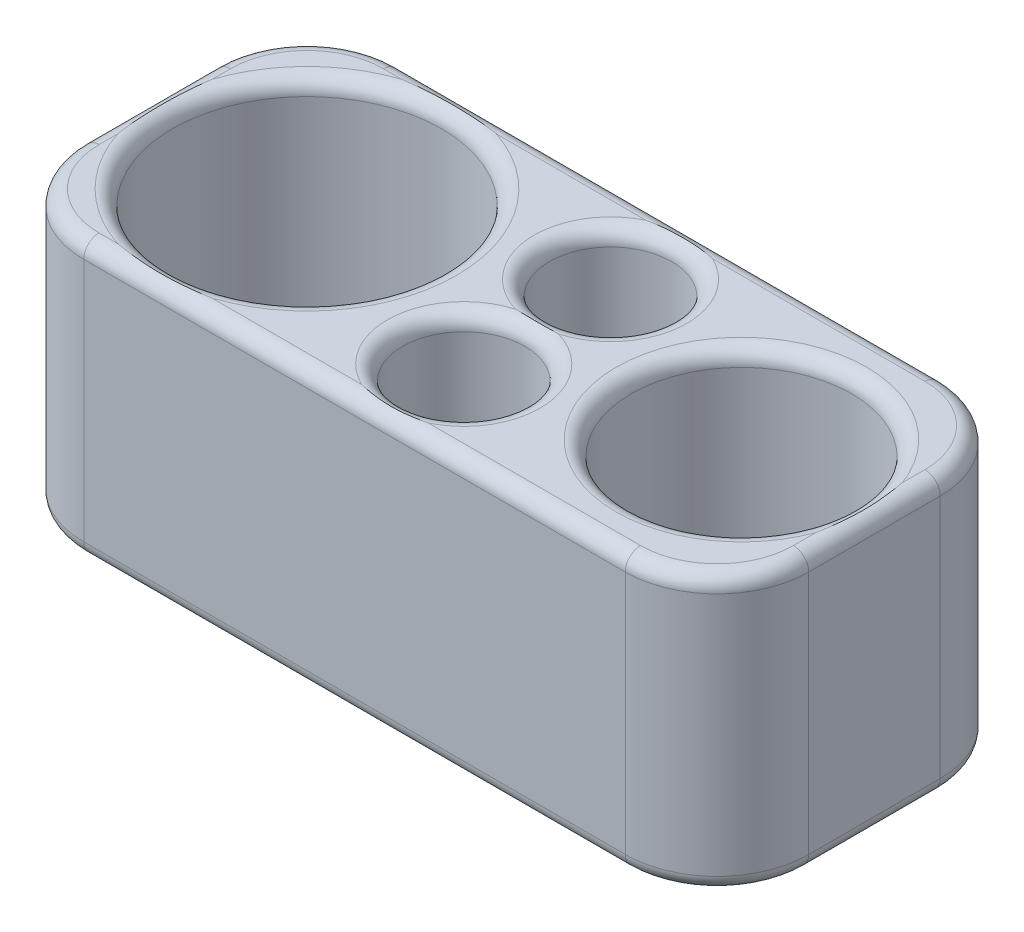
SolidWorks part; units mm, degrees
ref_plane "Front Plane" through (0, 0, 0) normal (0, 0, 1) x (1, 0, 0)
ref_plane "Top Plane" through (0, 0, 0) normal (0, 1, 0) x (1, 0, 0)
ref_plane "Right Plane" through (0, 0, 0) normal (1, 0, 0) x (0, 0, -1)
sketch "Sketch2" plane through (0, 0, 0) normal (0, 1, 0) x (1, 0, 0)
  line L0 (-7.9766, -4.2441) -> (-3.4391, -5.6909) construction
  line L1 (-35.2563, -13.97) -> (35.2563, -13.97) construction
  line L2 (-35.2563, -13.97) -> (-35.2563, 13.97) construction
  line L3 (-35.2563, 13.97) -> (35.2563, 13.97) construction
  line L4 (35.2563, -13.97) -> (35.2563, 13.97) construction
  line L5 (-35.2563, -13.97) -> (35.2563, 13.97) construction
  line L6 (-35.2563, 13.97) -> (35.2563, -13.97) construction
  line L7 (8.5869, -5.4735) -> (13.0691, -3.8637) construction
  line L8 (-37.6375, 16.3513) -> (37.6375, 16.3513)
  line L9 (37.6375, -16.3513) -> (37.6375, 16.3513)
  line L10 (-37.6375, -16.3513) -> (37.6375, -16.3513)
  line L11 (-37.6375, -16.3513) -> (-37.6375, 16.3513)
  circle A0 centre (-21.2863, 0) radius 13.97
  circle A2 centre (2.6107, -7.62) radius 6.35
  circle A3 centre (23.8263, 0) radius 11.43
  circle A5 centre (2.6107, 7.62) radius 6.35
  point P0 (0, 0)
  dimension "D1" = 27.94
  dimension "D2" = 22.86
  dimension "D3" = 12.7
  dimension "D4" = 4.7625
  dimension "D5" = 2.3813
extrude "Boss-Extrude1" add sketch "Sketch2" along normal blind 25.4
sketch "Sketch3" plane through (0, 0, 0) normal (0, -1, 0) x (1, 0, 0)
  line L4 (-37.6375, 16.3513) -> (-37.6375, -16.3513)
  line L5 (-37.6375, -16.3513) -> (37.6375, -16.3513)
  line L6 (37.6375, -16.3513) -> (37.6375, 16.3513)
  line L7 (37.6375, 16.3513) -> (-37.6375, 16.3513)
  line L8 (-37.6375, 16.3513) -> (-37.6375, -16.3513)
  line L9 (-37.6375, -16.3513) -> (37.6375, -16.3513)
  line L10 (37.6375, -16.3513) -> (37.6375, 16.3513)
  line L11 (37.6375, 16.3513) -> (-37.6375, 16.3513)
  dimension "D1" = 0
extrude "Boss-Extrude2" add sketch "Sketch3" along normal blind 3.175
fillet "Fillet2" radius 9.525 4 edges at (37.6375, 11.1125, -16.3513) (37.6375, 11.1125, 16.3513) (-37.6375, 11.1125, 16.3513) (-37.6375, 11.1125, -16.3513)
fillet "Fillet1" radius 1.5875 24 edges at (37.6375, -3.175, 0) (-37.6375, -3.175, 0) (0, -3.175, -16.3513) (0, -3.175, 16.3513) (23.8263, 25.4, 11.43) (2.6107, 25.4, 13.97) (2.6107, 25.4, -1.27) (-21.2863, 25.4, 13.97) (0, 25.4, -16.3513) (37.6375, 25.4, 0) (0, 25.4, 16.3513) (-37.6375, 25.4, 0) (23.8263, 0, 11.43) (2.6107, 0, 13.97) (2.6107, 0, -1.27) (-21.2863, 0, 13.97) (-34.8477, -3.175, 13.5614) (34.8477, -3.175, 13.5614) (34.8477, -3.175, -13.5614) (-34.8477, -3.175, -13.5614) (-34.8477, 25.4, -13.5614) (34.8477, 25.4, -13.5614) (34.8477, 25.4, 13.5614) (-34.8477, 25.4, 13.5614)
hole_wizard "CSK for #10 Flat Head Machine Screw (100)1" positions "3DSketch1" profile "Sketch4" countersink size "#10" standard "ANSI Inch" end condition through all
sketch3d "3DSketch1"
  line L0 (-21.2863, 9.4965, 0) -> (-21.2863, -14.2305, 0) construction
  line L1 (23.8263, 8.0611, 0) -> (23.8263, -11.3597, 0) construction
  point P0 (-21.2863, 0, 0)
  point P4 (23.8263, 0, 0)
sketch "Sketch4" plane through (-21.2863, 0, 0) normal (1, 0, 0) x (0, 0, 1)
  line L0 (0, 0) -> (0, 3.175)
  line L1 (0, 3.175) -> (2.5527, 3.175)
  line L2 (2.5527, 3.175) -> (2.5527, 1.9608)
  line L3 (2.5527, 1.9608) -> (4.8895, 0)
  line L5 (4.8895, 0) -> (0, 0)
  line L6 (-2.5527, 1.9608) -> (-4.8895, 0) construction
  line L11 (0, -6.35) -> (0, 107.95) construction
  dimension "Thru Hole Dia." = 5.1054
  dimension "Thru Hole Depth" = 3.175
  dimension "Near C'Sink Dia." = 9.779
  dimension "Near C'Sink Angle" = 100
